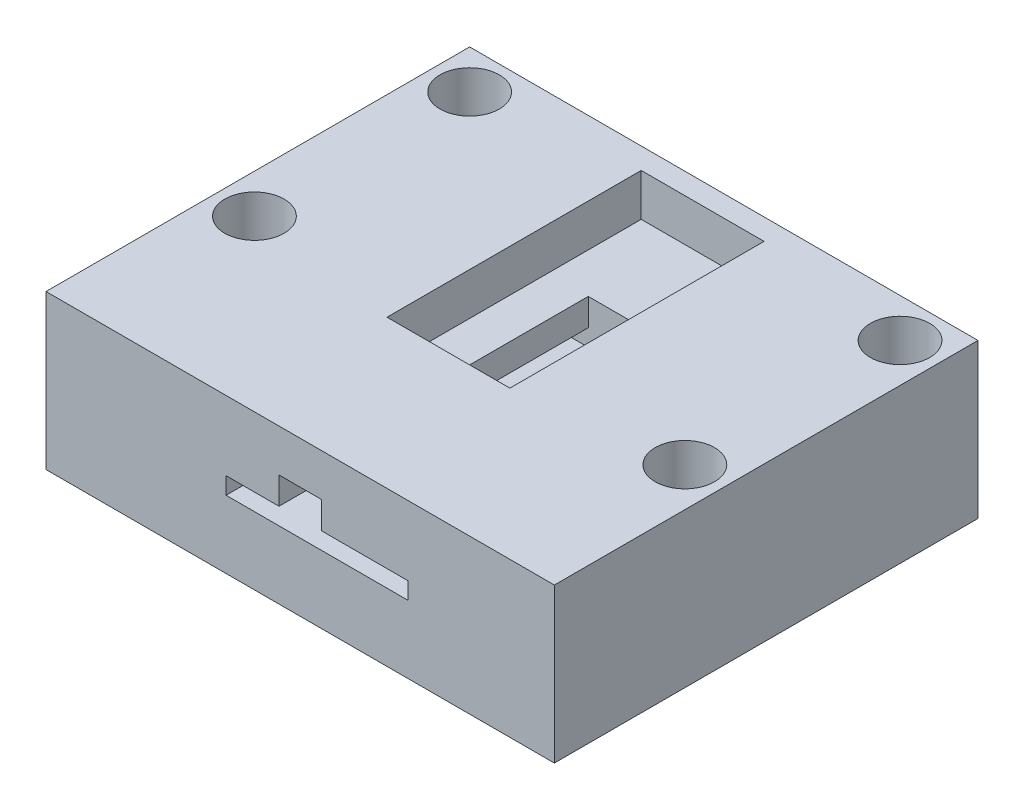
SolidWorks part; units mm, degrees
ref_plane "Front Plane" through (0, 0, 0) normal (0, 0, 1) x (1, 0, 0)
ref_plane "Top Plane" through (0, 0, 0) normal (0, 1, 0) x (1, 0, 0)
ref_plane "Right Plane" through (0, 0, 0) normal (1, 0, 0) x (0, 0, -1)
sketch "Sketch2" plane through (0, 0, 0) normal (0, 1, 0) x (1, 0, 0)
  line L1 (0, 0) -> (60, 0)
  line L2 (0, 0) -> (0, 50)
  line L3 (0, 50) -> (60, 50)
  line L4 (60, 0) -> (60, 50)
  dimension "D1" = 50
  dimension "D2" = 60
extrude "Boss-Extrude1" add sketch "Sketch2" along normal blind 10
sketch "Sketch3" plane through (0, 10, 0) normal (0, 1, 0) x (1, 0, 0)
  line L0 (60, 50) -> (0, 50) construction
  line L1 (21.25, 36.5) -> (42.75, 36.5)
  line L2 (21.25, 36.5) -> (21.25, 0)
  line L3 (21.25, 0) -> (42.75, 0)
  line L4 (42.75, 36.5) -> (42.75, 0)
  line L5 (0, 0) -> (60, 0) construction
  circle A0 centre (30, 32.5) radius 2.25 construction
  point P9 (30, 50)
  dimension "D4" = 4.5
  dimension "D1" = 21.5
  dimension "D3" = 4
  dimension "D5" = 8.75
  dimension "D6" = 17.5
extrude "Cut-Extrude2" cut sketch "Sketch3" against normal blind 2
sketch "Sketch4" plane through (0, 10, 0) normal (0, 1, 0) x (1, 0, 0)
  line L0 (27.5, 50) -> (27.5, 0)
  line L1 (0, 50) -> (60, 50)
  line L2 (0, 50) -> (0, 0)
  line L3 (0, 0) -> (60, 0)
  line L4 (60, 50) -> (60, 0)
  line L5 (32.5, 50) -> (32.5, 0)
  line L6 (27.5, 32.5) -> (32.5, 32.5)
  point P4 (39.5387, 33.9329)
  point P6 (0, 0)
  point P14 (30, 32.5)
  line M12 (0, 0) -> (21.25, 0)
  line M13 (21.25, 0) -> (21.25, 36.5)
  line M14 (21.25, 36.5) -> (42.75, 36.5)
  line M15 (42.75, 36.5) -> (42.75, 0)
  line M16 (42.75, 0) -> (60, 0)
  line M17 (60, 0) -> (60, 50)
  line M18 (60, 50) -> (0, 50)
  line M19 (0, 50) -> (0, 0)
  dimension "D1" = 5
extrude "Boss-Extrude2" add sketch "Sketch4" along normal blind 3.2 contours L5 M18 M14 M15 M16 M17 | L5 L3 M14 M15 | L3 L0 M13 M14 | L0 M18 M19 M12 M13 M14 | L5 L1 L0 M14 region at (24.375, 10, -18.25) region at (11.6366, 10, -26.3426) region at (30, 10, -43.25) region at (37.625, 10, -18.25) region at (49.474, 10, -27.5231)
sketch "Sketch5" plane through (0, 13.2, 0) normal (0, 1, 0) x (1, 0, 0)
  line L1 (0, 50) -> (60, 50)
  line L2 (0, 50) -> (0, 0)
  line L3 (0, 0) -> (60, 0)
  line L4 (60, 50) -> (60, 0)
  line L5 (22.75, 47.5) -> (37.25, 47.5)
  line L6 (22.75, 47.5) -> (22.75, 17.5)
  line L7 (22.75, 17.5) -> (37.25, 17.5)
  line L8 (37.25, 47.5) -> (37.25, 17.5)
  point P4 (30, 47.5)
  point P5 (37.25, 32.5)
  dimension "D1" = 30
  dimension "D2" = 14.5
extrude "Boss-Extrude3" add sketch "Sketch5" along normal blind 5
sketch "Sketch1" plane through (0, 13.2, 0) normal (0, 1, 0) x (1, 0, 0)
  line L5 (4.6, 45.4) -> (55.4, 45.4) construction
  line L6 (4.6, 45.4) -> (4.6, 20) construction
  line L7 (4.6, 20) -> (55.4, 20) construction
  line L8 (55.4, 45.4) -> (55.4, 20) construction
  line L9 (60, 50) -> (0, 50) construction
  line L10 (4.6, 45.4) -> (0, 45.4)
  line L12 (4.6, 45.4) -> (4.6, 50)
  line L13 (0, 50) -> (0, 0) construction
  circle A0 centre (4.6, 20) radius 3.5
  circle A1 centre (4.6, 45.4) radius 3.5
  circle A2 centre (55.4, 45.4) radius 3.5
  circle A3 centre (55.4, 20) radius 3.5
  point P0 (30, 50)
  point P1 (30, 45.4)
  point P4 (0, 0)
  point P13 (0, 0)
  point P14 (0, 0)
  point P15 (4.6, 49.4413)
  point P19 (0, 0)
  point P20 (0, 0)
  point P24 (0, 0)
  point P25 (0, 45.4)
  point P26 (0, 0)
  dimension "D3" = 7
  dimension "D1" = 25.4
  dimension "D2" = 50.8
extrude "Cut-Extrude1" cut sketch "Sketch1" against normal through all both and the other way through all contours L12 A1 L10 | L10 A1 L12 | A2 | A0 | A3 region at (5.0951, 13.2, -44.9049) region at (3.1146, 13.2, -46.8854) region at (4.6, 13.2, -20) region at (55.4, 13.2, -45.4) region at (55.4, 13.2, -20)
